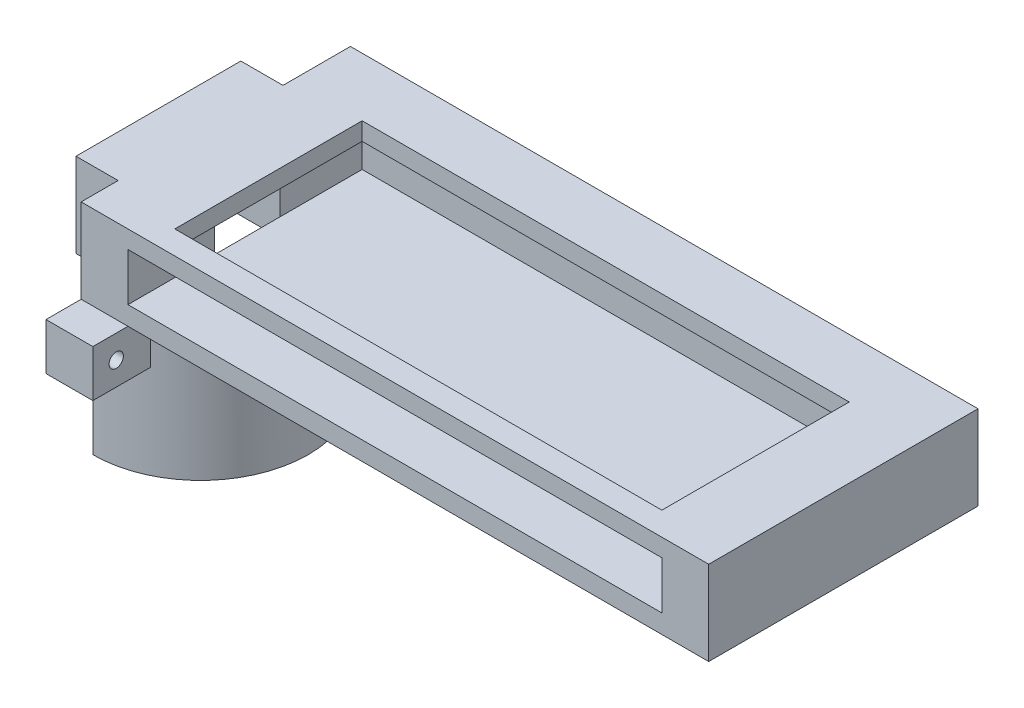
SolidWorks part; units mm, degrees
ref_plane "Front Plane" through (0, 0, 0) normal (0, 0, 1) x (1, 0, 0)
ref_plane "Top Plane" through (0, 0, 0) normal (0, 1, 0) x (1, 0, 0)
ref_plane "Right Plane" through (0, 0, 0) normal (1, 0, 0) x (0, 0, -1)
sketch "Sketch5" plane through (0, 0, 0) normal (0, 1, 0) x (1, 0, 0)
  line L1 (0, 0) -> (-134, 0)
  line L2 (0, 0) -> (0, 57.5)
  line L3 (0, 57.5) -> (-134, 57.5)
  line L4 (-134, 0) -> (-134, 57.5)
  line L5 (-10, 0) -> (-124, 0)
  line L6 (-10, 0) -> (-10, 50)
  line L7 (-10, 50) -> (-124, 50)
  line L8 (-124, 0) -> (-124, 50)
  dimension "D1" = 57.5
  dimension "D2" = 134
  dimension "D3" = 114
  dimension "D4" = 50
  dimension "D5" = 10
extrude "Main Body" add sketch "Sketch5" against normal blind 14 contours L1 L8 L7 L6 L2 L3 L4 region at (-5, 0, -1.4582)
sketch "Sketch6" plane through (0, 0, 0) normal (0, 1, 0) x (1, 0, 0)
  line L1 (-10, 50) -> (-124, 50)
  line L2 (-10, 50) -> (-10, 0)
  line L3 (-10, 0) -> (-124, 0)
  line L4 (-124, 50) -> (-124, 0)
extrude "Rail" add sketch "Sketch6" against normal blind 3.8
sketch "Sketch7" plane through (0, -3.8, 0) normal (0, -1, 0) x (1, 0, 0)
  line L0 (-124, -50) -> (-124, 0) construction
  line L1 (-15, -45) -> (-119, -45)
  line L2 (-15, -45) -> (-15, -5)
  line L3 (-15, -5) -> (-119, -5)
  line L4 (-119, -45) -> (-119, -5)
  line L5 (-10, -50) -> (-124, -50) construction
  line L6 (-10, 0) -> (-10, -50) construction
  line L7 (-124, 0) -> (-10, 0) construction
  dimension "D1" = 5
  dimension "D2" = 5
  dimension "D3" = 5
  dimension "D4" = 5
extrude "Window" cut sketch "Sketch7" against normal through all
sketch "Sketch8" plane through (0, 0, 0) normal (0, 0, 1) x (1, 0, 0)
  line L0 (-134, -14) -> (-134, 0) construction
  line L1 (0, -14) -> (-134, -14)
  line L2 (0, -14) -> (0, -18)
  line L3 (0, -18) -> (-134, -18)
  line L4 (-134, -14) -> (-134, -18)
  dimension "D1" = 4
extrude "Cover" add sketch "Sketch8" against normal up to surface (57.5 mm away) up to face at (-67, -7, -57.5)
sketch "Sketch9" plane through (-134, 0, 0) normal (-1, 0, 0) x (0, 0, 1)
  line L0 (-57.5, -18) -> (0, -18) construction
  line L1 (-18.5, -18) -> (-32.5, -18)
  line L2 (-18.5, -18) -> (-18.5, -4)
  line L3 (-18.5, -4) -> (-32.5, -4)
  line L4 (-32.5, -18) -> (-32.5, -4)
  line L5 (-57.5, -18) -> (-57.5, 0) construction
  dimension "D1" = 14
  dimension "D2" = 14
  dimension "D3" = 25
extrude "SiPM Window" cut sketch "Sketch9" against normal up to surface (10 mm away) up to face at (-124, -8.9, -25)
sketch "Sketch10" plane through (0, -18, 0) normal (0, -1, 0) x (1, 0, 0)
  line L0 (-134, -57.5) -> (-134, -32.5) construction
  line L4 (-134, -18.5) -> (-134, 0) construction
  line L5 (-134, -57.5) -> (0, -57.5) construction
  line L6 (-134, -5.5) -> (-134, -2.5)
  line L7 (-134, -45.5) -> (-134, -48.5)
  arc A0 (-134, -45.5) -> (-134, -5.5) centre (-134, -25.5) ccw
  arc A1 (-134, -48.5) -> (-134, -2.5) centre (-134, -25.5) ccw
  line M4 (-134, -32.5) -> (-134, -57.5)
  line M8 (-134, 0) -> (-134, -18.5)
  dimension "D2" = 20
  dimension "D1" = 32
  dimension "D3" = 3
  dimension "D4" = 3
extrude "Tube Adapter" add sketch "Sketch10" along normal blind 30 contours A1 A0 M4 M8 region at (-133.4857, -18, -4)
sketch "Sketch11" plane through (0, -18, 0) normal (0, -1, 0) x (1, 0, 0)
  line L1 (-134, -57.5) -> (-124, -57.5)
  line L2 (-134, -57.5) -> (-134, -48.5)
  line L4 (-124, -57.5) -> (-124, -46.2123)
  arc A0 (-134, -48.5) -> (-124, -46.2123) centre (-134, -25.5) ccw
  dimension "D1" = 10
extrude "Right Screw Terminal" add sketch "Sketch11" along normal blind 10
sketch "Sketch12" plane through (-134, 0, 0) normal (-1, 0, 0) x (0, 0, 1)
  line L0 (-48.5, -28) -> (-57.5, -28) construction
  line L1 (-57.5, -28) -> (-57.5, 0) construction
  circle A0 centre (-52.5, -23) radius 1.524
  dimension "D3" = 3.048
  dimension "D1" = 5
  dimension "D2" = 5
extrude "Right Screw Hole" cut sketch "Sketch12" against normal up to next
sketch "Sketch13" plane through (0, -18, 0) normal (0, -1, 0) x (-1, 0, 0)
  line L2 (134, 2.5) -> (134, -7.5)
  line L3 (134, -7.5) -> (124, -7.5)
  line L4 (124, 4.7877) -> (124, -7.5)
  arc A0 (134, 2.5) -> (124, 4.7877) centre (134, 25.5) cw
  dimension "D1" = 10
  dimension "D2" = 10
extrude "Left Screw Terminal" add sketch "Sketch13" along normal blind 10
sketch "Sketch14" plane through (-134, 0, 0) normal (-1, 0, 0) x (0, 0, 1)
  line L0 (7.5, -28) -> (7.5, -18) construction
  line L1 (7.5, -28) -> (-2.5, -28) construction
  circle A0 centre (2.5, -23) radius 1.524
  dimension "D3" = 3.048
  dimension "D1" = 5
  dimension "D2" = 5
extrude "Left Screw Hole" cut sketch "Sketch14" against normal up to next
sketch "Sketch15" plane through (-134, 0, 0) normal (-1, 0, 0) x (0, 0, 1)
  line L0 (-18.5, -18) -> (-5.5, -18) construction
  line L1 (-7.9, -18) -> (-43.1, -18)
  line L2 (-7.9, -18) -> (-7.9, 0)
  line L3 (-7.9, 0) -> (-43.1, 0)
  line L4 (-43.1, -18) -> (-43.1, 0)
  line L7 (0, 0) -> (-57.5, 0) construction
  line L8 (-32.5, -4) -> (-32.5, -18) construction
  dimension "D1" = 35.2
  dimension "D2" = 10.6
extrude "SiPM Mount" add sketch "Sketch15" along normal blind 9
sketch "Sketch17" plane through (0, -18, 0) normal (0, -1, 0) x (1, 0, 0)
  line L0 (-124, -18.5) -> (-134, -18.5) construction
  line L1 (-134, -9.9) -> (-139, -9.9)
  line L2 (-134, -9.9) -> (-134, -41)
  line L3 (-134, -41) -> (-139, -41)
  line L4 (-139, -9.9) -> (-139, -41)
  line L5 (-134, -32.5) -> (-134, -18.5) construction
  dimension "D1" = 31.1
  dimension "D2" = 8.6
  dimension "D3" = 5
extrude "Cut-Extrude1" cut sketch "Sketch17" against normal offset from surface (16 mm away) 2 up to face at (-67, 0, -25)
ref_plane "Plane1" through (-144, 0, 0) normal (-1, 0, 0) x (0, 0, 1)
sketch "Sketch18" plane through (-144, 0, 0) normal (-1, 0, 0) x (0, 0, 1)
  line L3 (-45.5, -48) -> (-45.5, -18) construction
  line L5 (-45.5, -48) -> (-5.5, -48) construction
  circle A0 centre (-25.5, -40.5) radius 1.524
  dimension "D1" = 3.048
  dimension "D2" = 20
  dimension "D3" = 7.5
extrude "Adapter Hole" cut sketch "Sketch18" against normal up to surface (32.9495 mm away) up to face at (-124.4677, -30.5, -25.5)
